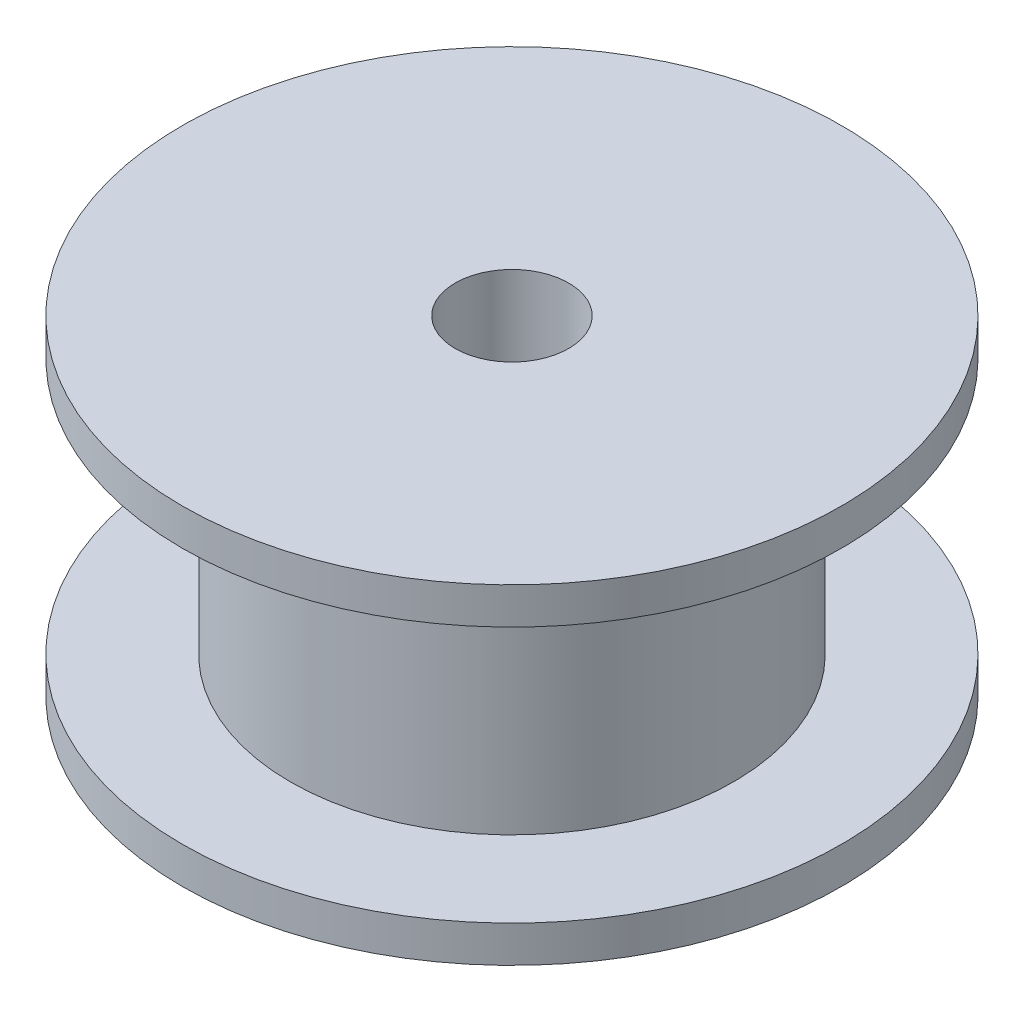
SolidWorks part; units mm, degrees
ref_plane "Alzado" through (0, 0, 0) normal (0, 0, 1) x (1, 0, 0)
ref_plane "Planta" through (0, 0, 0) normal (0, 1, 0) x (1, 0, 0)
ref_plane "Vista lateral" through (0, 0, 0) normal (1, 0, 0) x (0, 0, -1)
sketch "Croquis1" plane through (0, 0, 0) normal (0, 1, 0) x (1, 0, 0)
  circle A0 centre (0, 0) radius 1.55
  circle A1 centre (0, 0) radius 6.05
  circle A2 centre (0, 0) radius 9
  dimension "D1" = 3.1
  dimension "D2" = 12.1
  dimension "D3" = 18
extrude "Saliente-Extruir1" add sketch "Croquis1" along normal blind 1 contours A1 A0 | A2 A1 region at (-5.8789, 0, 0) region at (-8.7454, 0, 0)
extrude "Saliente-Extruir2" add sketch "Croquis1<3>" along normal blind 8 contours A1 | A0
sketch "Croquis1<3>" plane through (0, 0, 0) normal (0, 1, 0) x (1, 0, 0) same geometry as "Croquis1"
sketch "Croquis2" plane through (0, 8, 0) normal (0, 1, 0) x (1, 0, 0)
  circle A0 centre (0, 0) radius 9 construction
  circle A1 centre (0, 0) radius 6.05 construction
  circle A2 centre (0, 0) radius 9
  circle A3 centre (0, 0) radius 6.05
  circle M1 centre (0, 0) radius 6.05
  circle M2 centre (0, 0) radius 1.55
extrude "Saliente-Extruir3" add sketch "Croquis2" along normal blind 1 contours A2 M1 | M1 M2 region at (-8.7454, 8, 0) region at (-5.8789, 8, 0)
